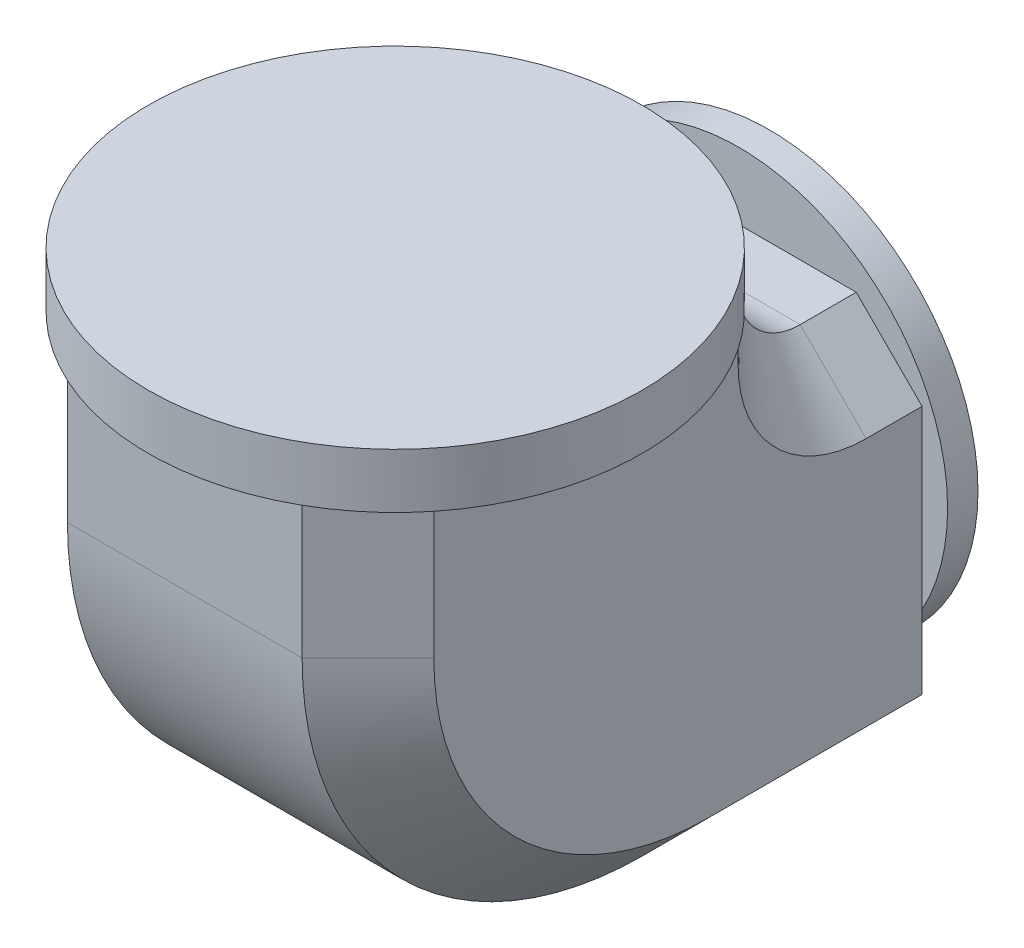
SolidWorks part; units mm, degrees
ref_plane "Front Plane" through (0, 0, 0) normal (0, 0, 1) x (1, 0, 0)
ref_plane "Top Plane" through (0, 0, 0) normal (0, 1, 0) x (1, 0, 0)
ref_plane "Right Plane" through (0, 0, 0) normal (1, 0, 0) x (0, 0, -1)
sketch "Sketch1" plane through (0, 0, 0) normal (0, 0, 1) x (1, 0, 0)
  circle A2 centre (0, 20.5854) radius 4.4271
extrude "Extrude1" add sketch "Sketch1" along normal blind 0.6447
sketch "Sketch2" plane through (0, 0, 0) normal (1, 0, 0) x (0, 0, -1)
  line L0 (-0.6447, 15.505) -> (-0.6447, 23.5931)
  line L1 (-0.6447, 23.5931) -> (-1.8329, 23.5931)
  line L2 (-3.1506, 24.9108) -> (-3.1506, 25.6508)
  line L3 (-3.1506, 25.6508) -> (-12.3984, 25.6508)
  line L4 (-12.3984, 25.6508) -> (-12.3984, 22.7498)
  line L5 (-5.1536, 15.505) -> (-0.6447, 15.505)
  line L6 (-0.6447, 25.0125) -> (-0.6447, 16.1582) construction
  arc A0 (-1.8329, 23.5931) -> (-3.1506, 24.9108) centre (-1.8329, 24.9108) cw
  arc A1 (-12.3984, 22.7498) -> (-5.1536, 15.505) centre (-5.1536, 22.7498) ccw
extrude "Extrude2" add sketch "Sketch2" along normal mid plane 7.7718
sketch "Sketch3" plane through (0, 25.6508, 0) normal (0, 1, 0) x (1, 0, 0)
  circle A0 centre (0, -7.9349) radius 5.2382
extrude "Extrude3" add sketch "Sketch3" along normal blind 1.1613
chamfer "Chamfer1" distance 1.397 angle 45 12 edges at (3.8859, 23.5931, 1.2388) (3.8859, 25.2808, 3.1506) (3.8859, 23.9791, 2.7647) (-3.8859, 23.5931, 1.2388) (-3.8859, 25.2808, 3.1506) (-3.8859, 23.9791, 2.7647) (3.8859, 24.2003, 12.3984) (3.8859, 15.505, 2.8991) (3.8859, 17.627, 10.2765) (-3.8859, 24.2003, 12.3984) (-3.8859, 15.505, 2.8991) (-3.8859, 17.627, 10.2765)
